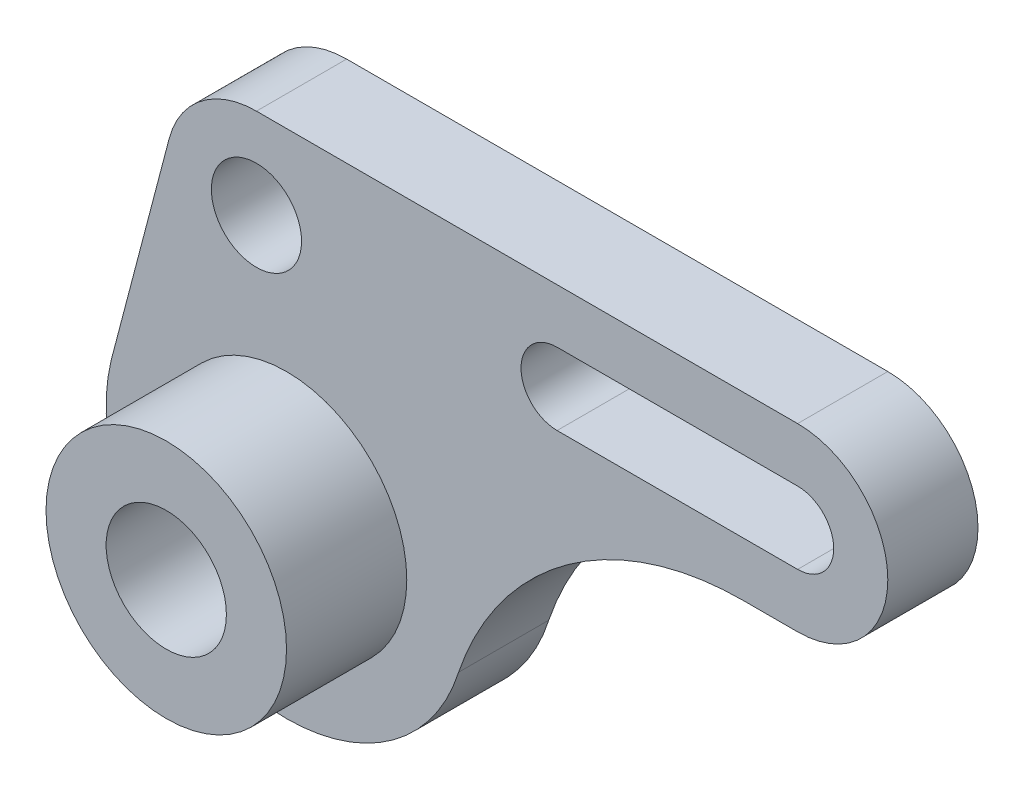
SolidWorks part; units mm, degrees
ref_plane "Ön Düzlem" through (0, 0, 0) normal (0, 0, 1) x (1, 0, 0)
ref_plane "Üst Düzlem" through (0, 0, 0) normal (0, 1, 0) x (1, 0, 0)
ref_plane "Sağ Düzlem" through (0, 0, 0) normal (1, 0, 0) x (0, 0, -1)
sketch "Çizim1" plane through (0, 0, 0) normal (0, 0, 1) x (1, 0, 0)
  line L0 (15.096, 44.8314) -> (55.096, 44.8314) construction
  line L1 (15.096, 50.8314) -> (55.096, 50.8314)
  line L2 (15.096, 38.8314) -> (55.096, 38.8314)
  line L4 (7.1466, 59.8314) -> (55.096, 59.8314)
  line L5 (46.0853, 29.8314) -> (55.096, 29.8314)
  line L7 (-34.904, 59.8314) -> (7.1466, 59.8314)
  line L8 (-59.0796, 11.8159) -> (-49.4124, 48.6402)
  circle A0 centre (-29.904, 4.8314) radius 10
  circle A1 centre (-29.904, 4.8314) radius 20
  arc A3 (46.0853, 29.8314) -> (-1.2894, -4.1799) centre (46.0853, -20.1686) ccw
  circle A4 centre (-34.904, 44.8314) radius 7.5
  arc A5 (-34.904, 59.8314) -> (-49.4124, 48.6402) centre (-34.904, 44.8314) ccw
  arc A6 (15.096, 50.8314) -> (15.096, 38.8314) centre (15.096, 44.8314) ccw
  arc A7 (55.096, 38.8314) -> (55.096, 50.8314) centre (55.096, 44.8314) ccw
  arc A9 (55.096, 29.8314) -> (55.096, 59.8314) centre (55.096, 44.8314) ccw
  arc A10 (-59.0796, 11.8159) -> (-1.2894, -4.1799) centre (-29.904, 4.8314) ccw
  point P11 (35.096, 44.8314)
  point P16 (31.1213, 44.8314)
  dimension "D1" = 20
  dimension "D2" = 40
  dimension "D3" = 85
  dimension "D4" = 100
  dimension "D5" = 15
  dimension "D6" = 30
  dimension "D7" = 6
  dimension "D10" = 15
  dimension "D11" = 40
  dimension "D12" = 30
  dimension "D8" = 40
  dimension "D9" = 50
extrude "Yükseklik-Ekstrüzyon1" add sketch "Çizim1" along normal blind 35 contours A1
extrude "Yükseklik-Ekstrüzyon2" add sketch "Çizim1<4>" along normal blind 15 contours L8 A10 A3 L5 A9 L4 L7 A5 A1 A4 A7 L2 A6 L1 region at (-5.5939, 29.0685, 0)
sketch "Çizim1<4>" plane through (0, 0, 0) normal (0, 0, 1) x (1, 0, 0) same geometry as "Çizim1"
extrude "Kes-Ekstrüzyon1" cut sketch "Çizim1<5>" along normal blind 35 contours A0
sketch "Çizim1<5>" plane through (0, 0, 0) normal (0, 0, 1) x (1, 0, 0) same geometry as "Çizim1"
